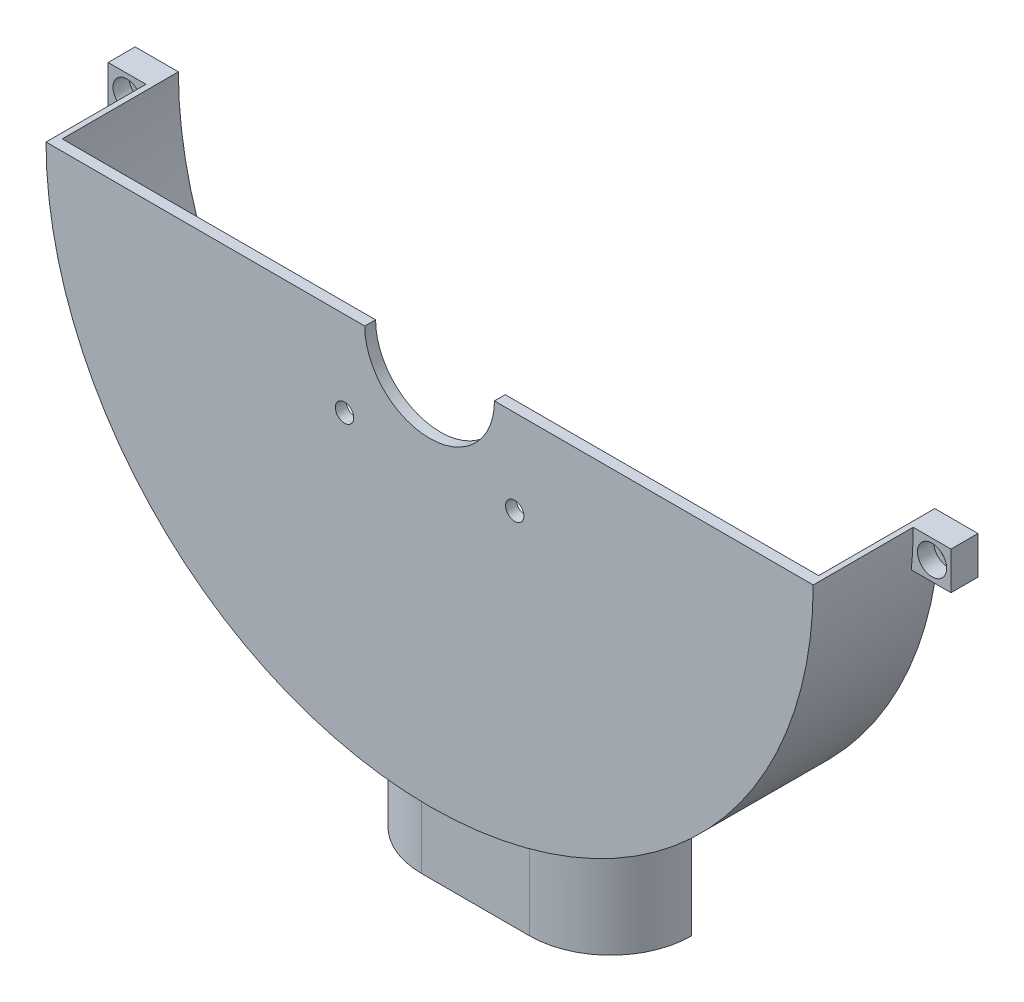
SolidWorks part; units mm, degrees
ref_plane "Front Plane" through (0, 0, 0) normal (0, 0, 1) x (1, 0, 0)
ref_plane "Top Plane" through (0, 0, 0) normal (0, 1, 0) x (1, 0, 0)
ref_plane "Right Plane" through (0, 0, 0) normal (1, 0, 0) x (0, 0, -1)
sketch "Sketch1" plane through (0, 0, 0) normal (0, 0, 1) x (1, 0, 0)
  line L0 (-71, 0) -> (71, 0)
  circle A0 centre (0, 0) radius 71
  circle A1 centre (0, 0) radius 70
  point P7 (0, 0)
extrude "Boss-Extrude1" add sketch "Sketch1" along normal blind 21.5 contours A1 L0 A0 region at (70.5, -1.5876, 0)
sketch "Sketch2" plane through (0, 0, 21.5) normal (0, 0, 1) x (1, 0, 0)
  line L0 (-80, 0) -> (80, 0)
  line L1 (-21.5, 0) -> (21.5, 0)
  circle A0 centre (0, 0) radius 80
  point P3 (0, 0)
  point P7 (0, 0)
  point P9 (0, 0)
  arc M1 (70, 0) -> (-70, 0) centre (0, 0) cw
  line M2 (-70, 0) -> (-71, 0)
  arc M3 (-71, 0) -> (71, 0) centre (0, 0) ccw
  line M4 (71, 0) -> (70, 0)
extrude "Boss-Extrude2" add sketch "Sketch2" along normal blind 2 contours M4 M1 M2 M3 | L0 M1 region at (-70.5, -1.5876, 21.5) region at (0, -29.7089, 21.5)
sketch "Sketch3" plane through (0, 0, 0) normal (0, 0, -1) x (-1, 0, 0)
  line L0 (-25, -71) -> (25, -71)
  line L1 (25, -71) -> (25, -66.453)
  line L2 (-25, -71) -> (-25, -66.453)
  line L3 (-25, -71) -> (-25, -91)
  line L4 (-25, -91) -> (25, -91)
  line L5 (25, -91) -> (25, -71)
  arc A0 (-71, 0) -> (71, 0) centre (0, 0) ccw construction
  arc A1 (-71, 0) -> (71, 0) centre (0, 0) ccw
  point P6 (0, -71)
  arc M5 (-71, 0) -> (71, 0) centre (0, 0) ccw
extrude "Boss-Extrude3" add sketch "Sketch3" against normal blind 15 contours L2 L0 M5 | L0 L1 M5 | L4 L5 L0 L3 region at (18.7907, -69.6437, 0) region at (0, -81, 0) region at (-18.7907, -69.6437, 0)
sketch "Sketch8" plane through (0, 0, 0) normal (0, 0, -1) x (-1, 0, 0)
  line L0 (-78, -7) -> (-72.2291, -7)
  line L1 (-71, 0) -> (-78, 0)
  line L3 (-73, -7) -> (-78, -7)
  line L4 (-78, 0) -> (-78, -7)
  line L6 (-71, 0) -> (-78, -7) construction
  line L7 (-73, -7) -> (-69.6491, -7)
  line L8 (-69.6491, -7) -> (-71, 0)
  line L9 (0, -70) -> (0, 0) construction
  line L10 (71, 0) -> (78, -7) construction
  line L11 (69.6491, -7) -> (71, 0)
  line L12 (73, -7) -> (69.6491, -7)
  line L13 (78, 0) -> (78, -7)
  line L14 (73, -7) -> (78, -7)
  line L15 (71, 0) -> (78, 0)
  line L16 (78, -7) -> (72.2291, -7)
  circle A0 centre (-74.5, -3.5) radius 1.6
  arc A1 (-70, 0) -> (70, 0) centre (0, 0) ccw construction
  circle A2 centre (74.5, -3.5) radius 1.6
  dimension "D1" = 7
  dimension "D2" = 7
extrude "Boss-Extrude5" add sketch "Sketch8" against normal blind 5 contours L11 L6 A0 L0 | L6 L1 L4 A0 | L0 L11 | L14 L12 L11 L15 L13 | A2 region at (72.7017, -4.7762, 0) region at (75.8015, -2.1985, 0)
sketch "Sketch10" plane through (0, 0, 5) normal (0, 0, 1) x (1, 0, 0)
  circle A0 centre (74.5, -3.5) radius 2.7
  circle A1 centre (-74.5, -3.5) radius 2.6
extrude "Cut-Extrude5" cut sketch "Sketch10" against normal blind 3
fillet "Fillet2" radius 15 2 edges at (-25, -78.7265, 15) (25, -78.7265, 15)
sketch "Sketch11" plane through (0, -91, 0) normal (0, -1, 0) x (1, 0, 0)
  line L0 (10, 12) -> (-10, 12)
  line L1 (-21.619, 3) -> (21.619, 3)
  line L2 (10, 15) -> (-10, 15)
  line L3 (-25, 0) -> (25, 0)
  line L4 (10, 15) -> (-10, 15)
  line L5 (-25, 0) -> (25, 0)
  line L6 (21.619, 3) -> (21.619, 0)
  line L7 (-21.619, 3) -> (-21.619, 0)
  arc A0 (-10, 12) -> (-21.619, 3) centre (-10, 0) ccw
  arc A1 (21.619, 3) -> (10, 12) centre (10, 0) ccw
  arc A2 (-10, 15) -> (-25, 0) centre (-10, 0) ccw
  arc A3 (25, 0) -> (10, 15) centre (10, 0) ccw
  arc A4 (-10, 15) -> (-25, 0) centre (-10, 0) ccw
  arc A5 (25, 0) -> (10, 15) centre (10, 0) ccw
  dimension "D1" = 0
  dimension "D2" = 3
extrude "Cut-Extrude7" cut sketch "Sketch11" against normal blind 20 contours L1 L7 L5 L6 | L1 A1 L0 A0 region at (0, -91, 7.1524) region at (0, -91, 1.5)
sketch "Sketch13" plane through (0, 0, 23.5) normal (0, 0, 1) x (1, 0, 0)
  line L0 (0, 0) -> (-15.75, -15.75) construction
  line L1 (0, 0) -> (15.75, -15.75) construction
  line L2 (-15.75, -15.75) -> (15.75, -15.75)
  circle A0 centre (0, 0) radius 22.2739
  circle A1 centre (-15.75, -15.75) radius 1.7
  circle A2 centre (15.75, -15.75) radius 1.7
extrude "Cut-Extrude8" cut sketch "Sketch13" against normal blind 10 contours A0 A2 | A1 | A2 region at (16.2518, -16.2518, 23.5)
sketch "Sketch14" plane through (0, 0, 23.5) normal (0, 0, 1) x (1, 0, 0)
  circle A0 centre (0, 0) radius 12
extrude "Cut-Extrude9" cut sketch "Sketch14" against normal blind 10
